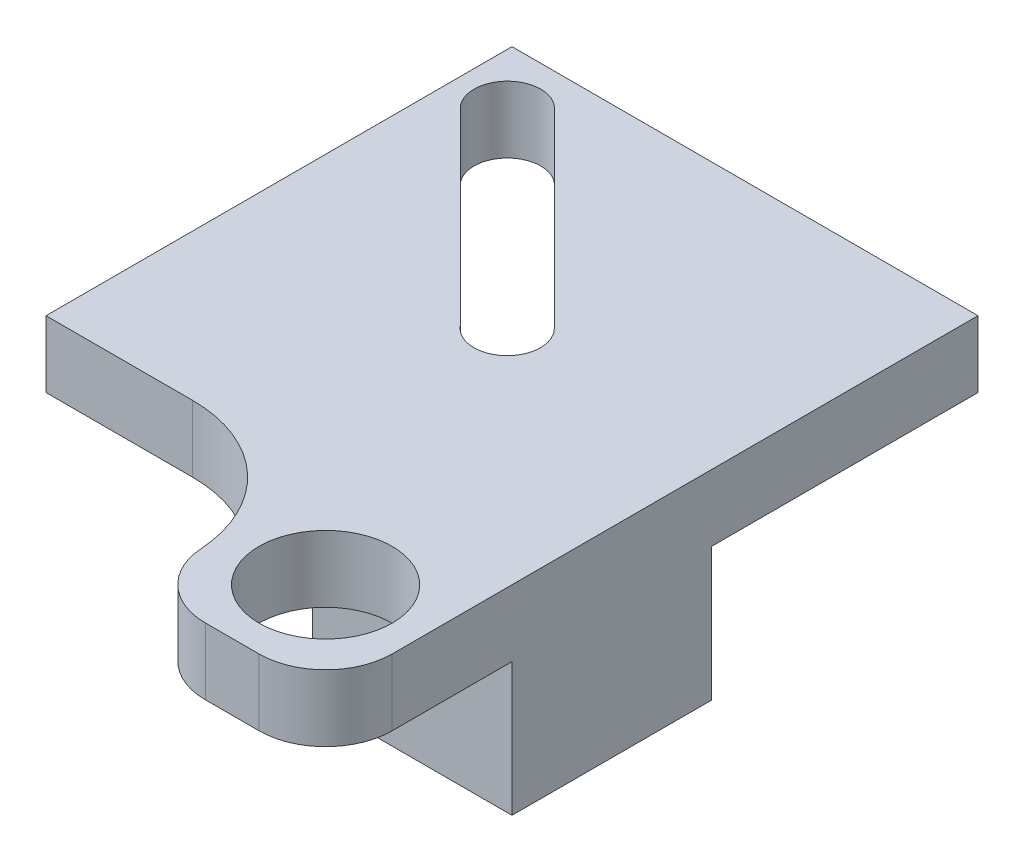
SolidWorks part; units mm, degrees
ref_plane "Front Plane" through (0, 0, 0) normal (0, 0, 1) x (1, 0, 0)
ref_plane "Top Plane" through (0, 0, 0) normal (0, 1, 0) x (1, 0, 0)
ref_plane "Right Plane" through (0, 0, 0) normal (1, 0, 0) x (0, 0, -1)
sketch "Sketch1" plane through (0, 0, 0) normal (0, 1, 0) x (1, 0, 0)
  line L2 (0, 0) -> (0, 35)
  line L10 (35, 35) -> (35, 0)
  line L11 (35, 35) -> (0, 35)
  line L13 (5.7773, 32.3996) -> (19.9194, 18.2575)
  line L15 (16.213, 14.9015) -> (2.0709, 29.0437)
  line L17 (35, 0) -> (35, -14)
  line L18 (35, -14) -> (21, -14)
  line L19 (21, -14) -> (21, 0)
  line L20 (21, 0) -> (0, 0)
  arc A2 (16.213, 14.9015) -> (19.9194, 18.2575) centre (18.1495, 16.4876) ccw
  arc A3 (5.7773, 32.3996) -> (2.0709, 29.0437) centre (3.8408, 30.8136) ccw
  circle A4 centre (28, -7) radius 5
  dimension "D3" = 10
  dimension "D4" = 14
  dimension "D7" = 7
  dimension "D8" = 7
  dimension "D1" = 35
  dimension "D2" = 35
  dimension "D5" = 5
  dimension "D6" = 20
  dimension "D9" = 14
  dimension "D10" = 45
  dimension "D11" = 45
extrude "Boss-Extrude1" add sketch "Sketch1" along normal blind 5
sketch "Sketch2" plane through (0, 0, 0) normal (0, -1, 0) x (1, 0, 0)
  line L3 (30, -5) -> (20, -5)
  line L4 (20, 0) -> (20, -5)
  line L7 (35, -15) -> (30, -15)
  line L8 (30, -5) -> (30, -15)
  line L20 (35, -15) -> (35, 0)
  line L21 (0, 0) -> (21, 0) construction
  line L22 (35, 0) -> (20, 0)
  line L23 (35, 14) -> (35, -35) construction
  dimension "D1" = 5
  dimension "D2" = 5
  dimension "D3" = 10
  dimension "D4" = 10
  dimension "D5" = 0
  dimension "D6" = 0
extrude "Boss-Extrude2" add sketch "Sketch2" along normal blind 10
fillet "Fillet1" radius 10 1 edges at (21, 2.5, 0)
fillet "Fillet4" radius 5 2 edges at (35, 2.5, 14) (21, 2.5, 14)
